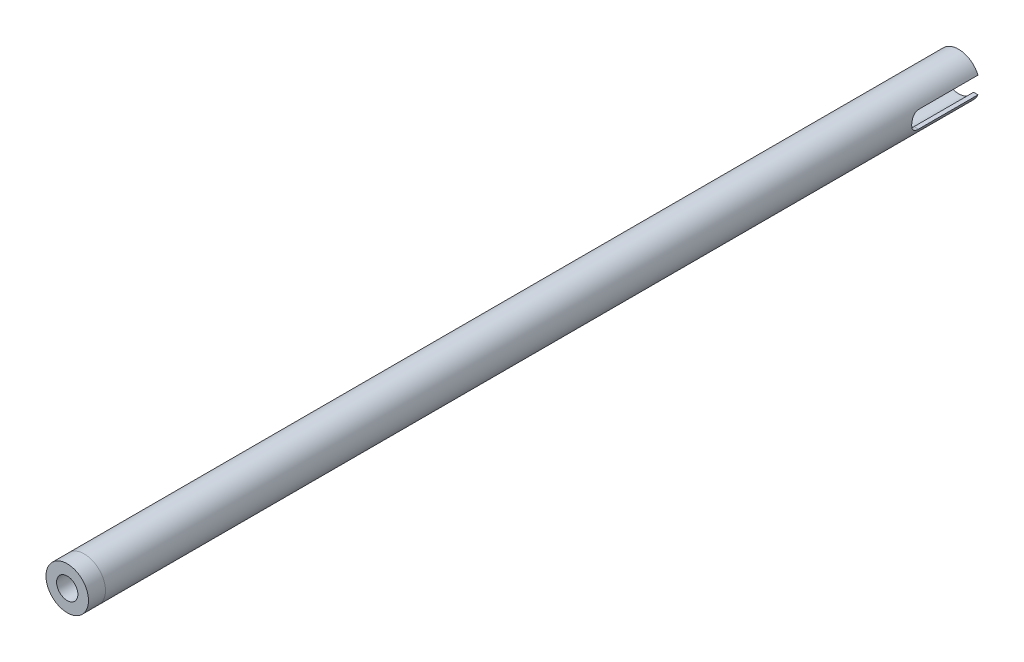
SolidWorks part; units mm, degrees
material "AISI 4130 Steel, normalized at 870C"
ref_plane "Front Plane" through (0, 0, 0) normal (0, 0, 1) x (1, 0, 0)
ref_plane "Top Plane" through (0, 0, 0) normal (0, 1, 0) x (1, 0, 0)
ref_plane "Right Plane" through (0, 0, 0) normal (1, 0, 0) x (0, 0, -1)
sketch "Axis" plane through (0, 0, 0) normal (0, 1, 0) x (1, 0, 0)
  line L0 (0, 0) -> (0, 332.6595) construction
  line L1 (0, 0) -> (0, -28.575) construction
  line L2 (0, 332.6595) -> (-7.9375, 332.6595) construction
  line L4 (0, 361.4112) -> (-10.3188, 324.0339) construction
  dimension "D1" = 28.575
  dimension "D2" = 7.9375
sketch "Sketch1" plane through (0, 0, 0) normal (0, 0, 1) x (1, 0, 0)
  line L0 (-7.9375, 0) -> (7.9375, 0) construction
  line L1 (-7.2748, 3.175) -> (7.2748, 3.175)
  line L2 (-7.2748, -3.175) -> (7.2748, -3.175)
  circle A0 centre (0, 0) radius 7.9375
  circle A1 centre (0, 0) radius 6.4643
  circle A2 centre (0, 0) radius 3.9688
  dimension "D1" = 15.875
  dimension "D3" = 7.9375
  dimension "D2" = 1.4732
  dimension "D4" = 6.35
extrude "Threaded insert 1-1" add sketch "Sketch1" against normal blind 6.35 contours A2 L1 A1 | A1 L1 A0 | A2 L0 A1 L1 | A1 L0 A0 L1 | L0 A1 L2 A0 | L0 A2 L2 A1 | A2 L2 A1 | A1 L2 A0 | L0 A1 L2 A2 | L0 A0 L2 A1 | A0 L0 A1 L1 | A1 L0 A2 L1 region at (4.8156, 1.6537, 0) region at (4.8156, -1.6537, 0) region at (6.9501, 1.6161, 0) region at (6.9501, -1.6161, 0) region at (-4.8156, -1.6537, 0) region at (-4.8156, 1.6537, 0) region at (0, 4.6361, 0) region at (0, -4.6361, 0) region at (0, 6.6174, 0) region at (6.4528, -3.3281, 0) region at (-6.9501, -1.6161, 0) region at (-6.9501, 1.6161, 0)
extrude "Threaded insert 1-2" add sketch "Sketch1<3>" against normal blind 9.525 from surface contours A2 L1 A1 | A2 L0 A1 L1 | L0 A2 L2 A1 | A2 L2 A1 | L0 A1 L2 A2 | A1 L0 A2 L1 region at (4.8156, 1.6537, 0) region at (4.8156, -1.6537, 0) region at (-4.8156, -1.6537, 0) region at (-4.8156, 1.6537, 0) region at (0, 4.6361, 0) region at (0, -4.6361, 0) starting at face at (7.9375, 0, -6.35)
sketch "Sketch1<3>" plane through (0, 0, 0) normal (0, 0, 1) x (1, 0, 0) same geometry as "Sketch1"
extrude "A-arm tube" add sketch "Sketch1<4>" against normal up to vertex (332.6595 mm away) from surface separate body contours A1 L1 A0 | A1 L0 A0 L1 | L0 A1 L2 A0 | A1 L2 A0 | L0 A0 L2 A1 | A0 L0 A1 L1 region at (6.9501, 1.6161, 0) region at (6.9501, -1.6161, 0) region at (0, 6.6174, 0) region at (6.4528, -3.3281, 0) region at (-6.9501, -1.6161, 0) region at (-6.9501, 1.6161, 0) up to point (0, 0, -332.6595) starting at face at (6.4643, 0, -6.35)
sketch "Sketch1<4>" plane through (0, 0, 0) normal (0, 0, 1) x (1, 0, 0) same geometry as "Sketch1"
extrude "Apex slot" cut sketch "Sketch1<5>" along normal blind 25.4 from surface contours A0 L0 A1 L1 | L0 A0 L2 A1 | A1 L0 A0 L1 | L0 A1 L2 A0 region at (6.9501, 1.6161, 0) region at (6.9501, -1.6161, 0) region at (-6.9501, -1.6161, 0) region at (-6.9501, 1.6161, 0) starting at face at (6.4643, 0, -332.6595)
sketch "Sketch1<5>" plane through (0, 0, 0) normal (0, 0, 1) x (1, 0, 0) same geometry as "Sketch1"
fillet "Fillet1" radius 3.175 4 edges at (-6.4528, 3.175, -307.2595) (-6.4528, -3.175, -307.2595) (6.4528, -3.175, -307.2595) (6.4528, 3.175, -307.2595)
equation "\"tube diameter\"= 5 / 8"
equation "\"tube thickness\"= .058"
equation "\"apex thickness\"= .25"
equation "\"tube slot\"= 1"
equation "\"D1@Sketch1\"=\"tube diameter\""
equation "\"D2@Sketch1\"=\"tube thickness\""
equation "\"threaded insert hole\"= .3125"
equation "\"D3@Sketch1\"=\"threaded insert hole\""
equation "\"D4@Sketch1\"=\"apex thickness\""
equation "\"D1@Apex slot\" = \"tube slot\""
equation "\"D1@Fillet1\"=\"apex thickness\"/2"
equation "\"D2@Axis\"=\"tube diameter\"/2"
